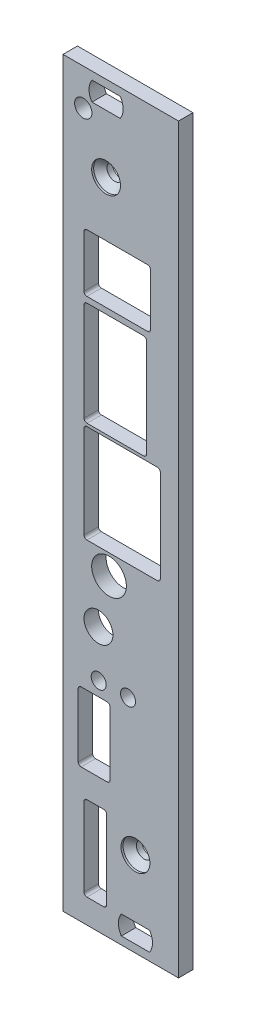
SolidWorks part; units mm, degrees
ref_plane "Front Plane" through (0, 0, 0) normal (0, 0, 1) x (1, 0, 0)
ref_plane "Top Plane" through (0, 0, 0) normal (0, 1, 0) x (1, 0, 0)
ref_plane "Right Plane" through (0, 0, 0) normal (1, 0, 0) x (0, 0, -1)
ref_plane "Plane1" through (0, 0, 2.5) normal (0, 0, 1) x (1, 0, 0)
sketch "Sketch1" plane through (0, 0, 2.5) normal (0, 0, 1) x (1, 0, 0)
  line L0 (12.53, 125.4) -> (-7.45, 125.4)
  line L1 (-7.45, 125.4) -> (-7.45, -3)
  line L2 (-7.45, -3) -> (12.53, -3)
  line L3 (12.53, -3) -> (12.53, 125.4)
extrude "Boss-Extrude1" add sketch "Sketch1" against normal blind 2.5
sketch "Sketch2" plane through (0, 0, 2.5) normal (0, 0, 1) x (1, 0, 0)
  line L0 (2.4454, 124.05) -> (-2.4454, 124.05)
  line L1 (-2.4454, 120.75) -> (2.4454, 120.75)
  arc A0 (-2.4454, 124.05) -> (-2.4454, 120.75) centre (0, 122.4) ccw
  arc A1 (2.4454, 120.75) -> (2.4454, 124.05) centre (0, 122.4) ccw
extrude "Cut-Extrude1" cut sketch "Sketch2" against normal through all
sketch "Sketch3" plane through (0, 0, 2.5) normal (0, 0, 1) x (1, 0, 0)
  line L0 (7.5254, 1.65) -> (2.6346, 1.65)
  line L1 (2.6346, -1.65) -> (7.5254, -1.65)
  arc A0 (2.6346, 1.65) -> (2.6346, -1.65) centre (5.08, 0) ccw
  arc A1 (7.5254, -1.65) -> (7.5254, 1.65) centre (5.08, 0) ccw
extrude "Cut-Extrude2" cut sketch "Sketch3" against normal through all
sketch "Sketch4" plane through (0, 0, 0) normal (0, 0, -1) x (-1, 0, 0)
  line L0 (3.82, 15.8) -> (-0.08, 15.8)
  line L1 (-0.08, 15.8) -> (-0.08, 1.2)
  line L2 (-0.08, 1.2) -> (3.82, 1.2)
  line L3 (3.82, 1.2) -> (3.82, 15.8)
extrude "Cut-Extrude3" cut sketch "Sketch4" against normal through all
hole_wizard "Ø3.0 (3) Diameter Hole1" positions "Sketch6" profile "Sketch5" hole size "Ø3.0" standard "ANSI Metric"
sketch "Sketch6" plane through (0, 0, 2.5) normal (0, 0, 1) x (1, 0, 0)
  point P0 (-3.95, 119.1)
sketch "Sketch5" plane through (-3.95, 119.1, 2.5) normal (1, 0, 0) x (0, -1, 0)
  line L0 (0, 0) -> (0, 2.5)
  line L1 (0, 2.5) -> (1.5, 2.5)
  line L2 (1.5, 2.5) -> (1.5, 0)
  line L5 (1.5, 0) -> (0, 0)
  line L11 (0, -6.35) -> (0, 107.95) construction
  dimension "Thru Hole Dia." = 3
  dimension "Thru Hole Depth" = 2.5
hole_wizard "CSK for M2.5 Flat Head Machine Screw1" positions "Sketch8" profile "Sketch7" countersink size "M2.5" standard "ANSI Metric"
sketch "Sketch8" plane through (0, 0, 2.5) normal (0, 0, 1) x (1, 0, 0)
  point P0 (5.08, 11.7)
  point P1 (0, 110.7)
sketch "Sketch7" plane through (5.08, 11.7, 2.5) normal (1, 0, 0) x (0, -1, 0)
  line L0 (0, 0) -> (0, 2.5)
  line L1 (0, 2.5) -> (1.35, 2.5)
  line L2 (1.35, 2.5) -> (1.35, 1.5)
  line L3 (1.35, 1.5) -> (2.5, 0.35)
  line L4 (2.5, 0.35) -> (2.5, 0)
  line L6 (2.5, 0) -> (0, 0)
  line L7 (-1.35, 1.5) -> (-2.5, 0.35) construction
  line L11 (0, -6.35) -> (0, 107.95) construction
  dimension "Thru Hole Dia." = 2.7
  dimension "Thru Hole Depth" = 2.5
  dimension "C'Sink Dia." = 5
  dimension "C'Sink Angle" = 90
  dimension "Head Clearance" = 0.35
ref_plane "Board bottom" through (0, 11.2, 0) normal (0, -1, 0) x (-1, 0, 0)
ref_plane "Board top" through (0, 111.2, 0) normal (0, 1, 0) x (1, 0, 0)
ref_plane "Board upper surface" through (-3.82, 0, 0) normal (1, 0, 0) x (0, 0, -1)
ref_plane "Board lower surface" through (-5.42, 0, 0) normal (1, 0, 0) x (0, 0, -1)
sketch "Sketch9" plane through (0, 0, 2.5) normal (0, 0, 1) x (1, 0, 0)
  line L0 (-3.82, 20.2) -> (-3.82, 32.2) construction
  line L1 (-3.82, 20.2) -> (0.68, 20.2)
  line L2 (-3.82, 32.2) -> (0.68, 32.2)
  line L3 (0.68, 20.2) -> (0.68, 32.2)
  line L4 (-3.82, -47.3899) -> (-3.82, 47.3899) construction
  line L5 (-28.8918, 11.2) -> (28.8918, 11.2) construction
  line L6 (-3.82, 32.2) -> (-3.82, 20.2) construction
  line L7 (-3.82, 32.2) -> (-4.82, 32.2)
  line L8 (-3.82, 20.2) -> (-4.82, 20.2)
  line L9 (-4.82, 32.2) -> (-4.82, 20.2)
  dimension "D1" = 9
  dimension "D2" = 21
  dimension "D3" = 4.5
  dimension "D4" = 1
extrude "USB" cut sketch "Sketch9" against normal through all
sketch "Sketch10" plane through (0, 0, 2.5) normal (0, 0, 1) x (1, 0, 0)
  line L0 (-3.82, 34.65) -> (3.8, 34.65) construction
  line L1 (-3.82, -47.3899) -> (-3.82, 47.3899) construction
  line L3 (-28.8918, 11.2) -> (28.8918, 11.2) construction
  circle A0 centre (-1.28, 34.65) radius 1.3
  circle A1 centre (3.8, 34.65) radius 1.3
  dimension "D1" = 2.6
  dimension "D2" = 2.6
  dimension "D3" = 2.54
  dimension "D4" = 5.08
  dimension "D5" = 23.45
extrude "LEDs" cut sketch "Sketch10" against normal through all
sketch "Sketch11" plane through (0, 0, 2.5) normal (0, 0, 1) x (1, 0, 0)
  line L0 (-1.32, 42.7) -> (-3.82, 42.7) construction
  line L1 (-3.82, -47.3899) -> (-3.82, 47.3899) construction
  line L3 (-28.8918, 11.2) -> (28.8918, 11.2) construction
  circle A0 centre (-1.32, 42.7) radius 2.5
  dimension "D1" = 5
  dimension "D2" = 2.5
  dimension "D3" = 31.5
extrude "Reset switch" cut sketch "Sketch11" against normal through all
sketch "Sketch13" plane through (0, 0, 2.5) normal (0, 0, 1) x (1, 0, 0)
  line L0 (0.505, 51.2) -> (-3.82, 51.2) construction
  line L1 (-3.82, -47.3899) -> (-3.82, 47.3899) construction
  line L2 (-28.8918, 11.2) -> (28.8918, 11.2) construction
  circle A0 centre (0.505, 51.2) radius 3
  dimension "D1" = 6
  dimension "D2" = 40
  dimension "D3" = 4.325
extrude "Disable comms" cut sketch "Sketch13" against normal through all
sketch "Sketch14" plane through (0, 0, 2.5) normal (0, 0, 1) x (1, 0, 0)
  line L0 (-3.82, 54.7) -> (-3.82, 71.7)
  line L1 (-3.82, 54.7) -> (9.38, 54.7)
  line L2 (-3.82, 71.7) -> (9.38, 71.7)
  line L3 (9.38, 54.7) -> (9.38, 71.7)
  line L4 (-3.82, -47.3899) -> (-3.82, 47.3899) construction
  line L5 (-28.8918, 11.2) -> (28.8918, 11.2) construction
  dimension "D1" = 43.5
  dimension "D2" = 60.5
  dimension "D3" = 13.2
extrude "RJ45" cut sketch "Sketch14" against normal through all
sketch "Sketch15" plane through (0, 0, 2.5) normal (0, 0, 1) x (1, 0, 0)
  line L0 (-3.82, 72.2) -> (-3.82, 90.2)
  line L1 (-3.82, 72.2) -> (6.98, 72.2)
  line L2 (-3.82, 90.2) -> (6.98, 90.2)
  line L3 (6.98, 72.2) -> (6.98, 90.2)
  line L4 (-3.82, -47.3899) -> (-3.82, 47.3899) construction
  line L5 (-28.8918, 11.2) -> (28.8918, 11.2) construction
  dimension "D1" = 61
  dimension "D2" = 79
  dimension "D3" = 10.8
extrude "Output" cut sketch "Sketch15" against normal through all
sketch "Sketch16" plane through (0, 0, 2.5) normal (0, 0, 1) x (1, 0, 0)
  line L0 (-3.82, 91.2) -> (-3.82, 101.2)
  line L1 (-3.82, 91.2) -> (7.68, 91.2)
  line L2 (-3.82, 101.2) -> (7.68, 101.2)
  line L3 (7.68, 91.2) -> (7.68, 101.2)
  line L4 (-3.82, -47.3899) -> (-3.82, 47.3899) construction
  line L5 (-28.8918, 11.2) -> (28.8918, 11.2) construction
  dimension "D1" = 80
  dimension "D2" = 90
  dimension "D3" = 11.5
extrude "Power" cut sketch "Sketch16" against normal through all
fillet "Fillets" radius 0.5 20 edges at (0.68, 20.2, 1.25) (-4.82, 20.2, 1.25) (-4.82, 32.2, 1.25) (0.68, 32.2, 1.25) (0.08, 1.2, 1.25) (-3.82, 1.2, 1.25) (-3.82, 15.8, 1.25) (0.08, 15.8, 1.25) (9.38, 71.7, 1.25) (6.98, 90.2, 1.25) (7.68, 101.2, 1.25) (-3.82, 71.7, 1.25) (-3.82, 90.2, 1.25) (-3.82, 101.2, 1.25) (-3.82, 54.7, 1.25) (-3.82, 72.2, 1.25) (-3.82, 91.2, 1.25) (9.38, 54.7, 1.25) (6.98, 72.2, 1.25) (7.68, 91.2, 1.25)
